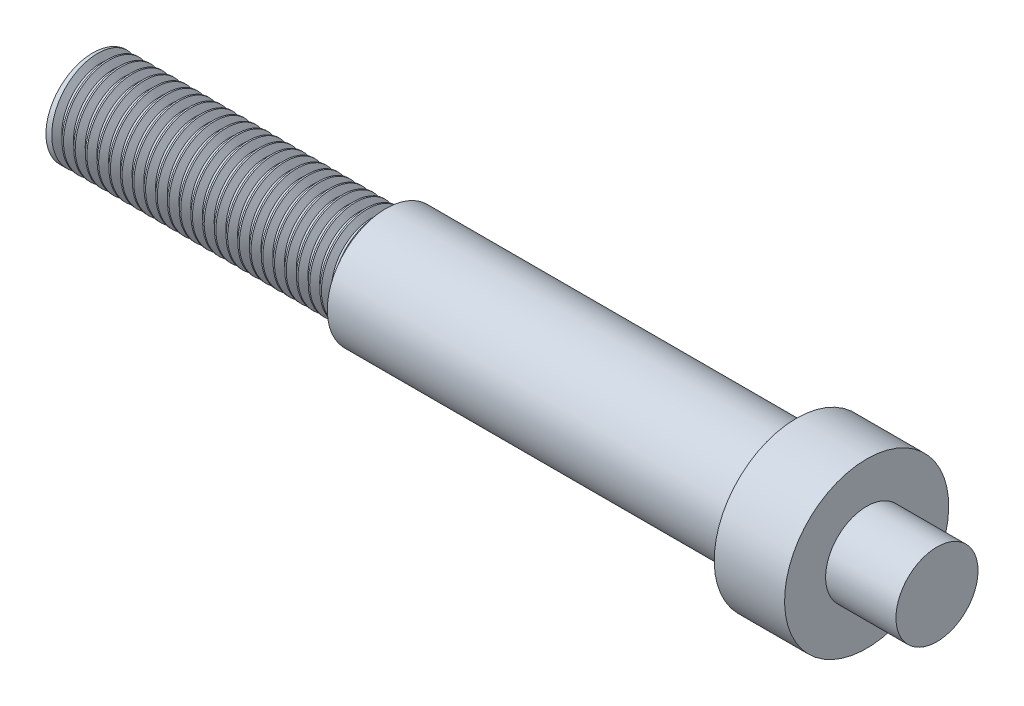
SolidWorks part; units mm, degrees
ref_plane "Front Plane" through (0, 0, 0) normal (0, 0, 1) x (1, 0, 0)
ref_plane "Top Plane" through (0, 0, 0) normal (0, 1, 0) x (1, 0, 0)
ref_plane "Right Plane" through (0, 0, 0) normal (1, 0, 0) x (0, 0, -1)
sketch "Sketch1" plane through (0, 0, 0) normal (0, 0, 1) x (1, 0, 0)
  line L0 (0, 0) -> (0, 4)
  line L1 (0, 4) -> (25, 4)
  line L2 (25, 4) -> (25, 5)
  line L3 (25, 5) -> (60, 5)
  line L4 (60, 5) -> (60, 7)
  line L5 (60, 7) -> (66, 7)
  line L6 (66, 7) -> (66, 3.5)
  line L7 (66, 3.5) -> (72, 3.5)
  line L8 (72, 3.5) -> (72, 0)
  line L9 (72, 0) -> (0, 0)
  dimension "D1" = 25
  dimension "D2" = 6
  dimension "D3" = 6
  dimension "D4" = 35
  dimension "D5" = 7
  dimension "D6" = 5
  dimension "D7" = 4
  dimension "D8" = 3.5
revolve "Revolve1" add sketch "Sketch1" angle 360 about L9
thread "Thread1" pitch 1 method cut profile "Thread Profile1" start angle 0, offset 0, length 25, pitch 1, diameter 8
ref_plane "Plane1" through (0, 0, -4) normal (0, -1, 0) x (0, 0, -1)
sketch "Thread Profile1" plane through (0, 0, -4) normal (0, -1, 0) x (0, 0, -1)
  line L0 (0, 0) -> (0, 1) construction
  line L11 (0, 0) -> (0, 0.875)
  line L12 (0, 0.875) -> (-0.5413, 0.5625)
  line L13 (-0.5413, 0.5625) -> (-0.5413, 0.3125)
  line L15 (-0.5413, 0.3125) -> (0, 0)
  line L17 (-0.5413, 0.4375) -> (0, 0.4375) construction
  point P2 (0, 0)
  dimension "Pitch" = 1
  dimension "Profile_Angle" = 60
  dimension "Profile_Land" = 0.25
  dimension "Profile_Height" = 0.5413
